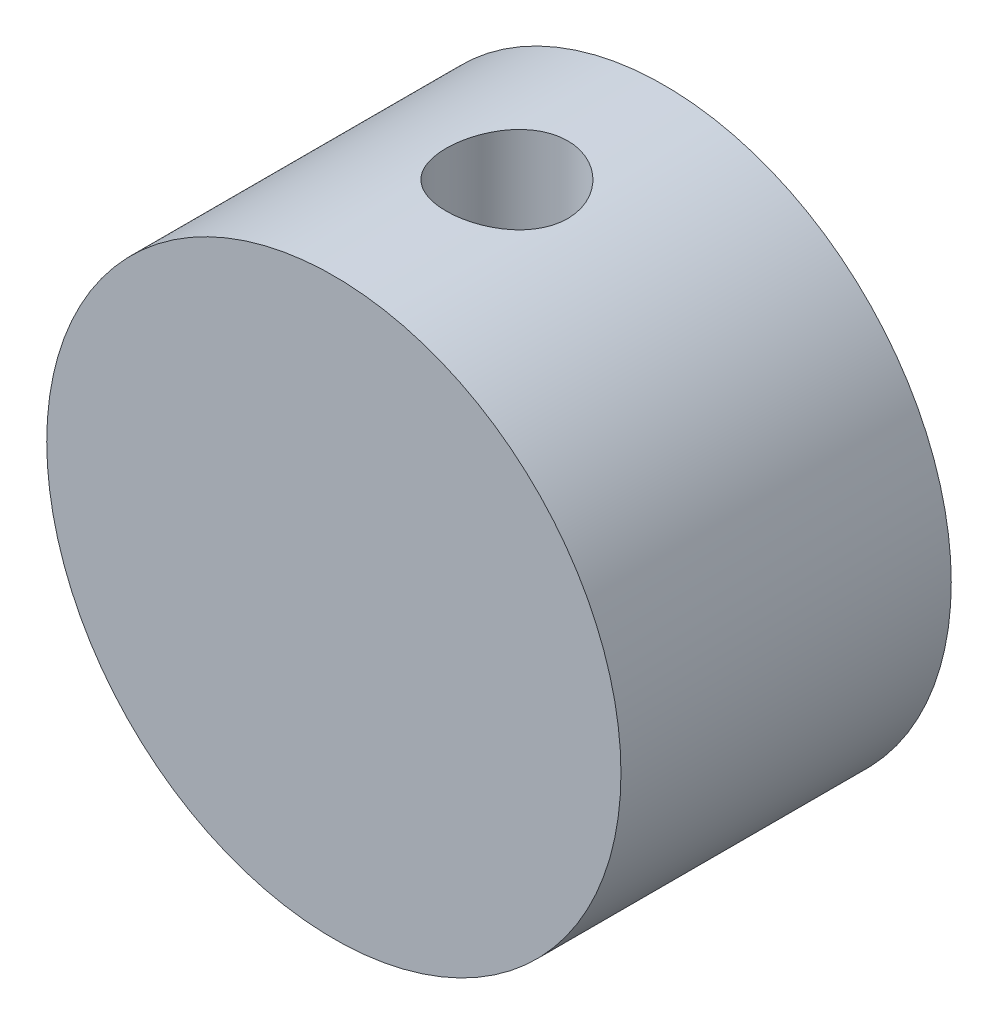
SolidWorks part; units mm, degrees
ref_plane "Front Plane" through (0, 0, 0) normal (0, 0, 1) x (1, 0, 0)
ref_plane "Top Plane" through (0, 0, 0) normal (0, 1, 0) x (1, 0, 0)
ref_plane "Right Plane" through (0, 0, 0) normal (1, 0, 0) x (0, 0, -1)
sketch "Sketch1" plane through (0, 0, 0) normal (0, 0, 1) x (1, 0, 0)
  circle A0 centre (0, 0) radius 16.515
  point P10 (0, 0)
  point P13 (0, 0)
  dimension "D1" = 33.03
extrude "Boss-Extrude1" add sketch "Sketch1" along normal blind 19
sketch "Sketch2" plane through (0, 0, 0) normal (0, 1, 0) x (1, 0, 0)
  circle A0 centre (0, -9.0452) radius 3.5
  dimension "D1" = 7
extrude "Cut-Extrude1" cut sketch "Sketch2" along normal through all
sketch "Sketch3" plane through (0, 0, 0) normal (0, 0, 1) x (1, 0, 0)
  line L0 (0, 0) -> (-17.3205, 10)
  line L1 (0, 0) -> (0, 9.6127) construction
  dimension "D1" = 20
  dimension "60" = 60
ref_plane "Plane1" through (-17.3205, 10, 0) normal (-0.866, 0.5, 0) x (0, 0, 1)
sketch "Sketch4" plane through (-17.3205, 10, 0) normal (-0.866, 0.5, 0) x (0, 0, 1)
  line L0 (0, -173205.0808) -> (0, 173213.4056) construction
  circle A0 centre (9.5, 0) radius 1
  point P2 (0, 0)
  dimension "D2" = 2
  dimension "D1" = 9.5
extrude "Cut-Extrude2" cut sketch "Sketch4" against normal blind 19 contours A0
ref_axis "Axis1" through (0, 0, 19) along (0, 0, -1)
